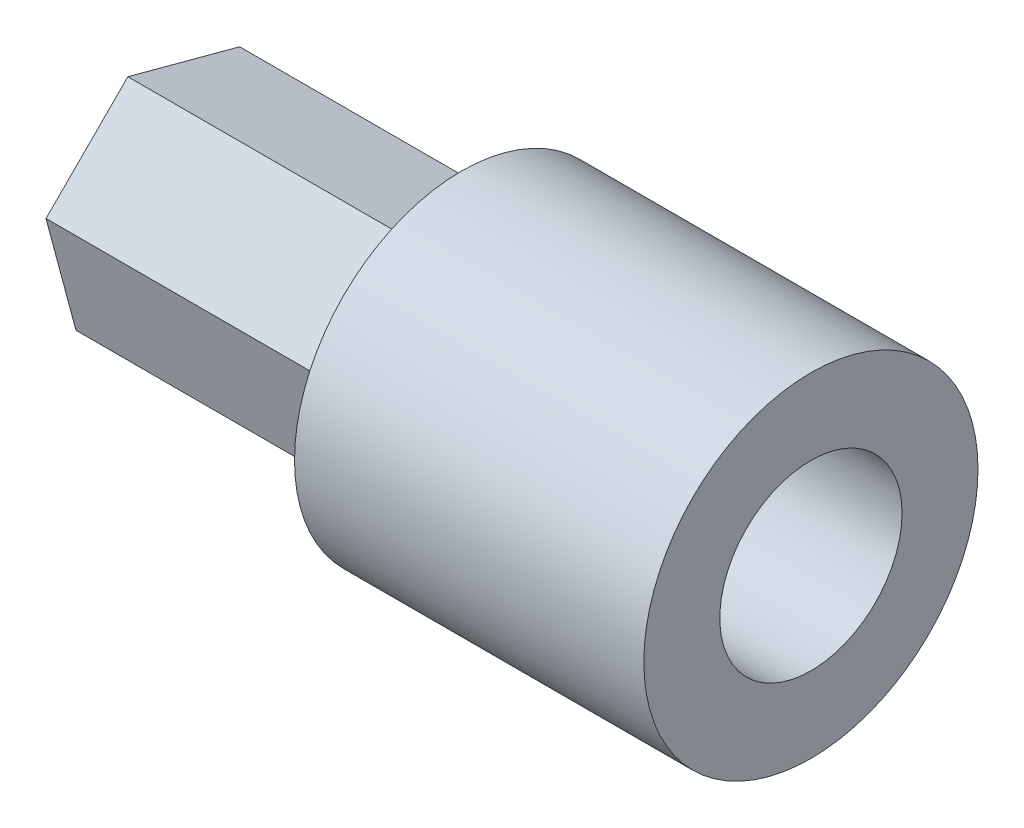
SolidWorks part; units mm, degrees
ref_plane "前视基准面" through (0, 0, 0) normal (0, 0, 1) x (1, 0, 0)
ref_plane "上视基准面" through (0, 0, 0) normal (0, 1, 0) x (1, 0, 0)
ref_plane "右视基准面" through (0, 0, 0) normal (1, 0, 0) x (0, 0, -1)
sketch "草图2" plane through (0, 0, 0) normal (1, 0, 0) x (0, 0, -1)
  line L1 (2.6944, 2.6944) -> (-0.9862, 3.6807)
  line L2 (-0.9862, 3.6807) -> (-3.6807, 0.9862)
  line L3 (-3.6807, 0.9862) -> (-2.6944, -2.6944)
  line L4 (-2.6944, -2.6944) -> (0.9862, -3.6807)
  line L5 (0.9862, -3.6807) -> (3.6807, -0.9862)
  line L6 (3.6807, -0.9862) -> (2.6944, 2.6944)
  circle A0 centre (0, 0) radius 1.5
  circle A1 centre (0, 0) radius 3.3 construction
  dimension "D1" = 3
  dimension "D2" = 6.6
extrude "凸台-拉伸1" add sketch "草图2" along normal blind 10 contours A0 | L5 L6 L1 L2 L3 L4 A0 region at (0, 0.8272, -3.087) region at (0, 0, 0)
extrude "切除-拉伸1" cut sketch "草图2<3>" along normal blind 4.5 contours A0 region at (0, 0, 0)
sketch "草图2<3>" plane through (0, 0, 0) normal (1, 0, 0) x (0, 0, -1) same geometry as "草图2"
sketch "草图3" plane through (10, 0, 0) normal (1, 0, 0) x (0, 0, -1)
  circle A0 centre (0, 0) radius 5.5
  dimension "D1" = 11
extrude "凸台-拉伸2" add sketch "草图3" along normal blind 11.5
sketch "草图4" plane through (21.5, 0, 0) normal (1, 0, 0) x (0, 0, -1)
  circle A0 centre (0, 0) radius 3
  dimension "D1" = 6
extrude "切除-拉伸2" cut sketch "草图4" against normal blind 9.5
